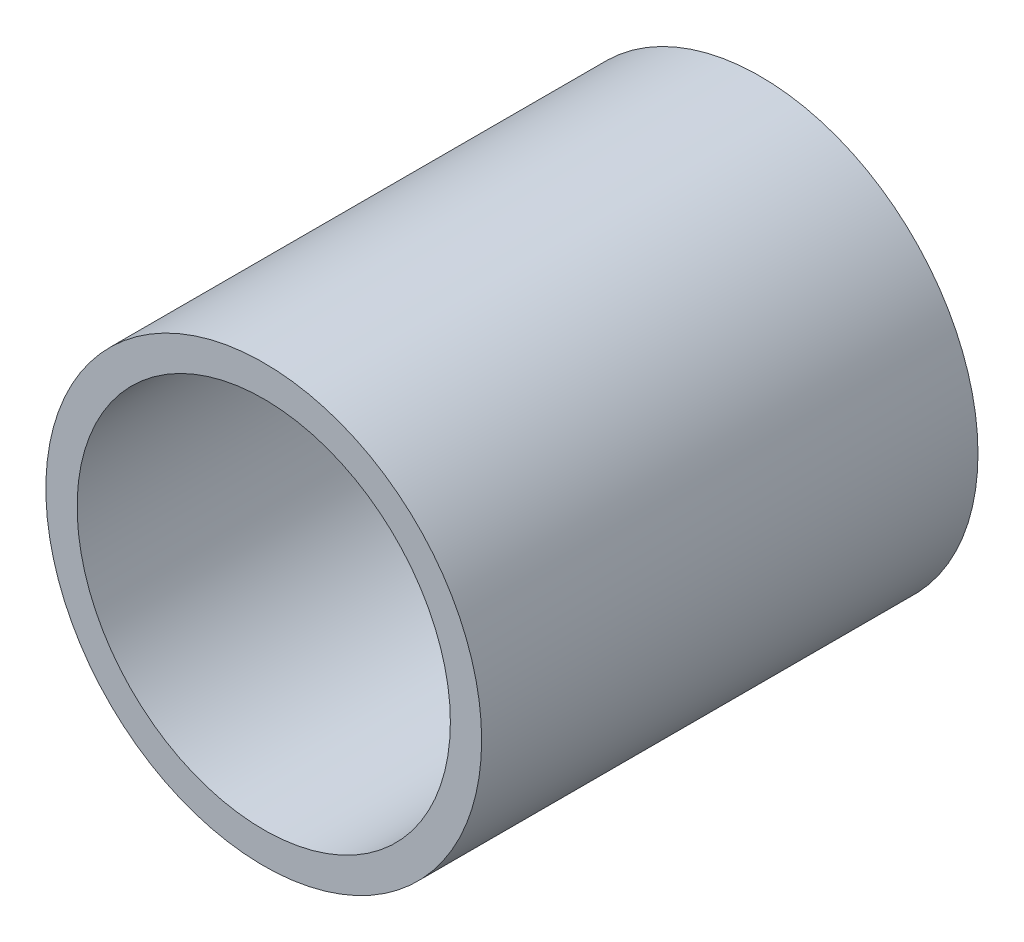
SolidWorks part; units mm, degrees
material "Commercial Bronze, UNS C22000 (90-10 Bronze)"
ref_plane "Front Plane" through (0, 0, 0) normal (0, 0, 1) x (1, 0, 0)
ref_plane "Top Plane" through (0, 0, 0) normal (0, 1, 0) x (1, 0, 0)
ref_plane "Right Plane" through (0, 0, 0) normal (1, 0, 0) x (0, 0, -1)
sketch "Sketch1" plane through (0, 0, 0) normal (0, 0, 1) x (1, 0, 0)
  circle A0 centre (0, 0) radius 5.5753
  circle A1 centre (0, 0) radius 4.7752
  dimension "OD" = 11.1506
  dimension "ID" = 9.5504
sketch "Sketch2" plane through (0, 0, 0) normal (1, 0, 0) x (0, 0, -1)
  line L2 (6.35, 0) -> (-6.35, 0) construction
  line L4 (-6.35, -5.5753) -> (-6.35, 5.5753) construction
  line L5 (-6.35, -4.7752) -> (6.35, -4.7752)
  line L6 (6.35, 4.7752) -> (-6.35, 4.7752)
  line L7 (6.35, -5.5753) -> (6.35, 5.5753) construction
  line L8 (-6.35, 5.5753) -> (6.35, 5.5753) construction
  line L9 (-6.35, -5.5753) -> (6.35, -5.5753) construction
  line L10 (0, 5.5753) -> (0, -5.5753) construction
  line L11 (0, 4.7752) -> (0, -4.7752) construction
  point P4 (0, -4.7752)
  point P7 (0, 4.7752)
  point P8 (0, 0)
  point P12 (-6.35, 0)
  point P15 (6.35, 0)
  point P16 (0, -5.5753)
  point P17 (0, 5.5753)
  dimension "Length" = 12.7
sketch "Sketch5" plane through (0, 0, 0) normal (0, 0, 1) x (1, 0, 0)
  circle A1 centre (0, 0) radius 4.7752
  circle A2 centre (0, 0) radius 4.7752
  circle A3 centre (0, 0) radius 5.5753
  circle A4 centre (0, 0) radius 5.5753
  dimension "D1" = 0
  dimension "D2" = 0
extrude "Boss-Extrude1" add sketch "Sketch5" along normal up to vertex and the other way up to vertex up to point (0, 0, 6.35) other way up to point (0, 0, -6.35)
sketch "Sketch4" plane through (0, 0, 6.35) normal (0, 0, 1) x (1, 0, 0)
  line L0 (0, 0) -> (-3.3766, 3.3766)
  line L2 (0, -5.5753) -> (0, 5.5753) construction
  circle A1 centre (0, 0) radius 4.7752 construction
  dimension "D1" = 45
equation "\"D1\"= \"Length@Sketch2\""
